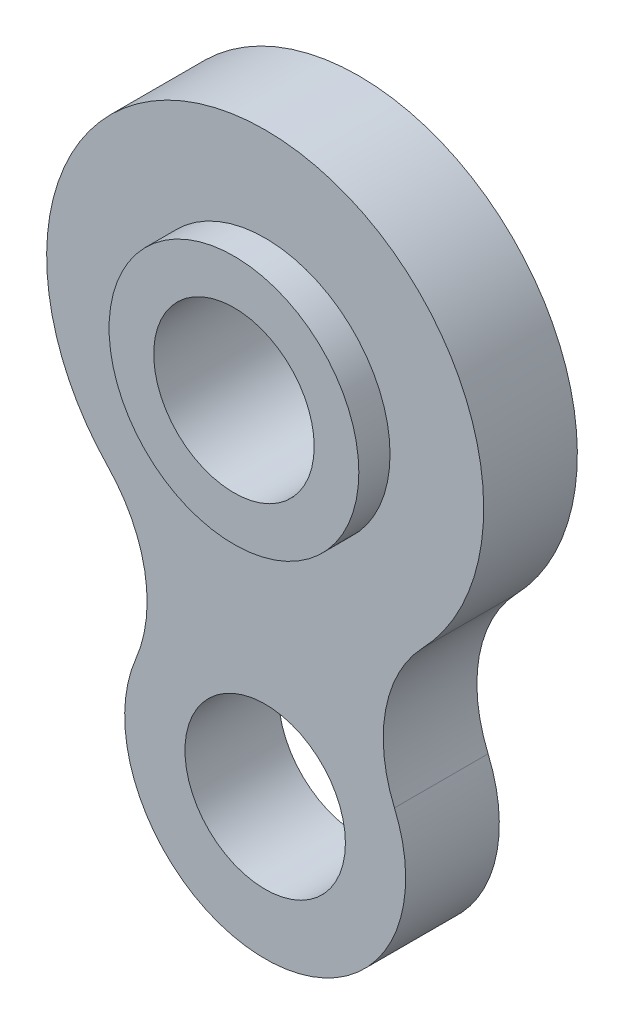
SolidWorks part; units mm, degrees
material "ABS"
ref_plane "Front Plane" through (0, 0, 0) normal (0, 0, 1) x (1, 0, 0)
ref_plane "Top Plane" through (0, 0, 0) normal (0, 1, 0) x (1, 0, 0)
ref_plane "Right Plane" through (0, 0, 0) normal (1, 0, 0) x (0, 0, -1)
sketch "Sketch1" plane through (0, 0, 0) normal (0, 0, 1) x (1, 0, 0)
  line L2 (0, 5.5562) -> (0, -5.5562) construction
  line L6 (0, 5.5562) -> (0, -12.7) construction
  line L9 (17.4625, 13.4938) -> (11.1125, 13.4938)
  line L10 (11.1125, 13.4938) -> (11.1125, 5.5563)
  line L11 (17.4625, 13.4938) -> (17.4625, -5.5562)
  line L12 (17.4625, -5.5562) -> (0, -5.5562)
  line L13 (11.1125, 5.5563) -> (11.1125, -5.5563) construction
  line L14 (14.2875, 13.4938) -> (14.2875, -5.5563) construction
  line L15 (14.2875, 7.9058) -> (14.2875, 0.0318)
  line L16 (0, 5.5562) -> (11.1125, 5.5563)
  line L17 (15.875, -5.5563) -> (15.875, -5.1309)
  line L18 (12.7, -5.5563) -> (15.875, -5.5563)
  line L19 (12.7, -5.5563) -> (12.7, -6.3691)
  line L20 (12.7, -6.3691) -> (15.875, -6.3691)
  line L21 (15.875, -5.5563) -> (15.875, -6.3691)
  circle A0 centre (0, 0) radius 5.5562 construction
  arc A2 (0, 5.5562) -> (0, -5.5562) centre (0, 0) ccw
  circle A4 centre (0, 0) radius 1.7859
  circle A16 centre (14.2875, 7.9058) radius 1.5875
  circle A20 centre (14.2875, 0.0318) radius 1.5875
  circle A22 centre (0, 0) radius 12.7 construction
  circle A25 centre (0, 0) radius 9.1281 construction
  circle A29 centre (14.2875, 10.3188) radius 3.175
  circle A30 centre (14.2875, -2.3813) radius 3.175
  circle A32 centre (0, -9.1281) radius 3.5719
  circle A33 centre (0, -9.1281) radius 1.7859
  circle A34 centre (-6.5741, -6.3327) radius 3.5719
  circle A35 centre (7.1437, -9.1281) radius 3.5719
  point P17 (14.2875, -5.5563)
  point P20 (14.2875, 3.9688)
  dimension "D1" = 7.874
  dimension "D2" = 11.1125
  dimension "D3" = 3.5719
  dimension "D5" = 6.35
  dimension "D6" = 7.1437
  dimension "D8" = 3.175
  dimension "D9" = 0.8128
  dimension "D11" = 3.5719
  dimension "D4" = 19.05
  dimension "D10" = 3.175
sketch "Sketch2" plane through (0, 0, 0) normal (0, 0, 1) x (1, 0, 0)
  circle A0 centre (0, 0) radius 5.5562
  circle A1 centre (0, -9.1281) radius 3.5719
  circle A2 centre (-6.5741, -6.3327) radius 3.5719
  circle A5 centre (0, 0) radius 2.0399
  circle A6 centre (0, -9.1281) radius 2.0399
  circle A7 centre (0, 0) radius 9.1281 construction
  circle A13 centre (6.5741, -6.3327) radius 3.5719
  arc A18 (0, 5.5562) -> (0, -5.5562) centre (0, 0) ccw construction
  circle A19 centre (0, 0) radius 3.175
  dimension "D1" = 4.0799
  dimension "D2" = 4.0799
  dimension "D3" = 6.35
extrude "Boss-Extrude1" add sketch "Sketch2" along normal blind 2.3812 contours A1 A6 | A2 A1 A0 | A13 A0 A1 | A0 A19 region at (5.0072, -2.0194, 0) region at (-2.4105, -5.669, 0) region at (2.4105, -5.669, 0) region at (1.9148, -6.2332, 0)
extrude "Boss-Extrude2" add sketch "Sketch2<6>" along normal blind 3.175 contours A19 A5 region at (-3.0852, 0, 0)
sketch "Sketch2<6>" plane through (0, 0, 0) normal (0, 0, 1) x (1, 0, 0) same geometry as "Sketch2"
